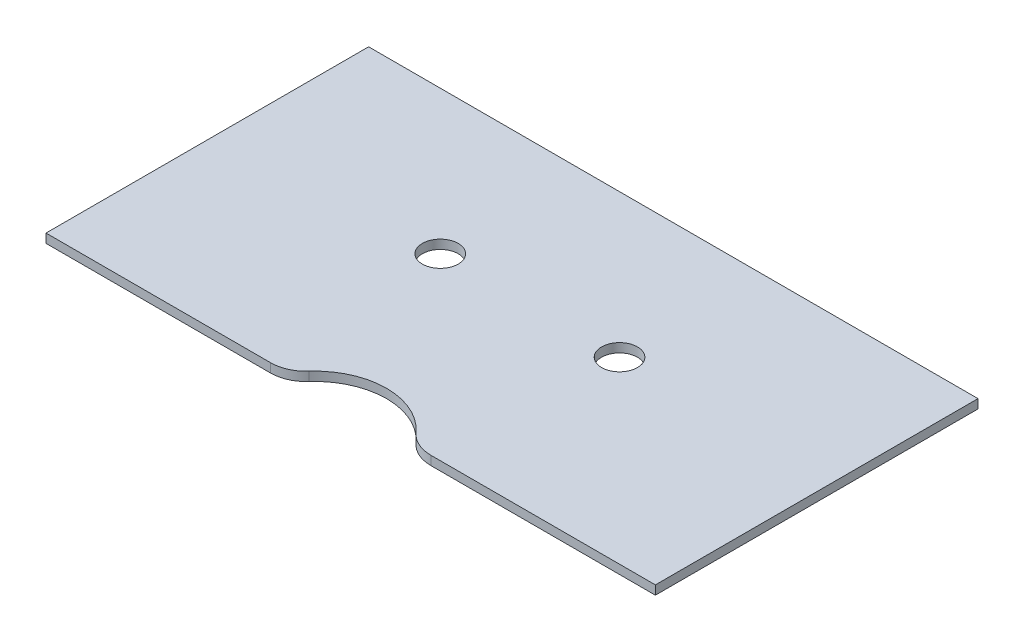
SolidWorks part; units mm, degrees
ref_plane "Front Plane" through (0, 0, 0) normal (0, 0, 1) x (1, 0, 0)
ref_plane "Top Plane" through (0, 0, 0) normal (0, 1, 0) x (1, 0, 0)
ref_plane "Right Plane" through (0, 0, 0) normal (1, 0, 0) x (0, 0, -1)
sketch "Sketch1" plane through (0, 0, 0) normal (0, 1, 0) x (1, 0, 0)
  line L0 (0, 114.3) -> (0, 0)
  line L1 (0, 0) -> (215.9, 0)
  line L2 (0, 0) -> (0, 254)
  line L3 (0, 254) -> (215.9, 254)
  line L4 (215.9, 0) -> (215.9, 254)
  line L5 (0, 139.7) -> (85.953, 139.7)
  line L6 (0, 139.7) -> (0, 114.3)
  line L7 (0, 114.3) -> (85.953, 114.3)
  line L8 (85.953, 139.7) -> (85.953, 114.3)
  line L9 (215.9, 139.7) -> (129.947, 139.7)
  line L10 (215.9, 139.7) -> (215.9, 114.3)
  line L11 (215.9, 114.3) -> (129.947, 114.3)
  line L12 (129.947, 139.7) -> (129.947, 114.3)
  line L13 (215.9, 0) -> (215.9, 114.3)
  circle A0 centre (107.95, 127) radius 25.4
  point P13 (85.953, 127)
  point P18 (0, 127)
  dimension "D4" = 50.8
  dimension "D5" = 85.953
  dimension "D1" = 254
  dimension "D2" = 215.9
  dimension "D3" = 25.4
extrude "Boss-Extrude1" add sketch "Sketch1" along normal blind 3.175 contours A0 L9 L4 L3 L2 L5 region at (107.95, 0, -197.6977)
sketch "Sketch2" plane through (0, 3.175, 0) normal (0, 1, 0) x (1, 0, 0)
  line L0 (0, 203.2) -> (76.2, 203.2) construction
  line L2 (76.2, 203.2) -> (139.7, 203.2) construction
  line L3 (0, 254) -> (215.9, 254) construction
  line L4 (215.9, 139.7) -> (215.9, 254) construction
  line L5 (139.7, 203.2) -> (215.9, 203.2) construction
  line L8 (0, 139.7) -> (0, 254) construction
  circle A0 centre (76.2, 203.2) radius 6.35
  circle A1 centre (139.7, 203.2) radius 6.35
  point P4 (0, 0)
  point P5 (215.9, 203.2)
  point P12 (0, 0)
  point P13 (0, 203.2)
  point P14 (93.6822, 203.2)
  point P15 (0, 203.2)
  dimension "D1" = 12.7
  dimension "D2" = 50.8
  dimension "D3" = 63.5
extrude "Cut-Extrude1" cut sketch "Sketch2" against normal through all
fillet "Fillet1" radius 12.7 2 edges at (129.947, 1.5875, -139.7) (85.953, 1.5875, -139.7)
